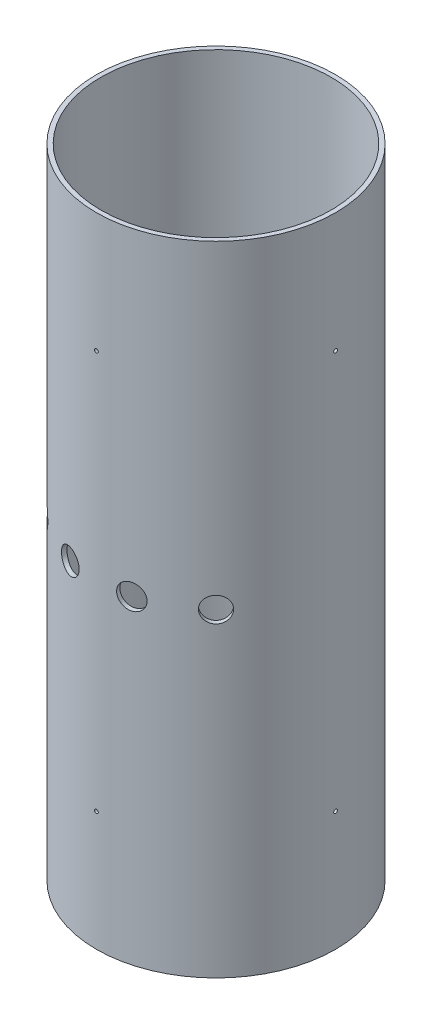
SolidWorks part; units mm, degrees
material "E-Glass Fiber"
ref_plane "Front Plane" through (0, 0, 0) normal (0, 0, 1) x (1, 0, 0)
ref_plane "Top Plane" through (0, 0, 0) normal (0, 1, 0) x (1, 0, 0)
ref_plane "Right Plane" through (0, 0, 0) normal (1, 0, 0) x (0, 0, -1)
sketch "Coupler Profile" plane through (0, 0, 0) normal (0, 1, 0) x (1, 0, 0)
  circle A0 centre (0, 0) radius 73.3425
  circle A1 centre (0, 0) radius 76.1746
  dimension "D1" = 146.685
  dimension "D2" = 152.3492
extrude "Coupler Body" add sketch "Coupler Profile" along normal blind 406.4
sketch "Sketch1" plane through (0, 0, 0) normal (0, 0, 1) x (1, 0, 0)
  line L0 (76.1746, 406.4) -> (-76.1746, 406.4) construction
  circle A0 centre (0, 76.2) radius 1.1906
  circle A1 centre (0, 330.2) radius 1.1906
  dimension "D3" = 2.3813
  dimension "D1" = 76.2
  dimension "D2" = 76.2
extrude "Cut-Extrude1" cut sketch "Sketch1" against normal through all both and the other way through all
pattern_circular "CirPattern1" count 4 over 360 about axis through (0, 0, 0) along (0, 1, 0) of "Cut-Extrude1"
sketch "Center Axis" plane through (0, 0, 0) normal (0, 0, 1) x (1, 0, 0)
  line L0 (0, 0) -> (0, 406.4) construction
  line L1 (73.3425, 406.4) -> (-73.3425, 406.4) construction
ref_plane "Offset Plane" through (0, 0, 0) normal (0.7071, 0, 0.7071) x (0, 1, 0)
sketch "Sketch3" plane through (0, 0, 0) normal (0.7071, 0, 0.7071) x (0, 1, 0)
  line L0 (0, 0) -> (406.4, 0) construction
  circle A0 centre (203.2, 0) radius 7.9375
  dimension "D1" = 15.875
extrude "Key Hole Cuts" cut sketch "Sketch3" along normal through all
pattern_circular "Key Hole Pattern" count 4 over 90 about axis through (0, 406.4, 0) along (0, 1, 0) of "Key Hole Cuts" reverse direction yes
sketch "Sketch4" plane through (0, 0, 0) normal (0, 0, 1) x (1, 0, 0)
  line L0 (-76.1746, 203.2) -> (76.1746, 203.2) construction
  line L1 (-76.1746, 329.0094) -> (-76.1746, 77.3906) construction
  line L2 (76.1746, 77.3906) -> (76.1746, 329.0094) construction
  circle A0 centre (0, 203.2) radius 3.175
  dimension "D1" = 6.35
extrude "Cut-Extrude2" cut sketch "Sketch4" against normal through all
ref_plane "Plane1" through (0, 330.1997, 0) normal (0, 1, 0) x (1, 0, 0)
sketch3d "3DSketch1"
  line L0 (-76.1746, 75.0094, 0) -> (0, 75.0094, 0) construction
  line L1 (0, 75.0094, 76.1746) -> (0, 75.0094, 0) construction
  spline S0 degree 3 poles (-76.1746, 75.0094, 0) (-76.1746, 75.0094, -0.0427) (-76.1745, 75.0132, -0.1253) (-76.1743, 75.0292, -0.2372) (-76.1738, 75.0564, -0.3498) (-76.1732, 75.0948, -0.4579) (-76.1726, 75.1441, -0.5614) (-76.1718, 75.2044, -0.6603) (-76.1709, 75.2758, -0.7547) (-76.1691, 75.4343, -0.9279) (-76.1662, 75.7306, -1.136) (-76.1648, 76.2008, -1.2181) (-76.1662, 76.6709, -1.1353) (-76.1694, 76.999, -0.9042) (-76.1718, 77.1995, -0.6651) (-76.1733, 77.3106, -0.4597) (-76.1743, 77.3758, -0.2422) (-76.1746, 77.3906, -0.0839) (-76.1746, 77.3906, 0) knots 0 0 0 0 0.032462 0.063988 0.094874 0.125434 0.155995 0.186881 0.218407 0.250871 0.375638 0.5004 0.625047 0.749699 0.813547 0.874851 0.936154 1 1 1 1 construction
  point P8 (0.1395, 77.3885, -0.0764)
  point P9 (1.6806, 75.0094, 0)
sketch "Sketch6" plane through (0, 330.1997, 0) normal (0, 1, 0) x (1, 0, 0)
  line L0 (0, 0) -> (-80.3653, 0)
  line L1 (0, 0) -> (0, -78.5899)
equation "\"Length\"=16"
equation "\"Outer Diameter\"= 5.998"
equation "\"Inner Diameter\"= 5.775"
equation "\"Wall Thickness\"= 0.111"
equation "\"D1@Coupler Profile\" = \"Inner Diameter\""
equation "\"D2@Coupler Profile\" = \"Outer Diameter\""
equation "\"D1@Coupler Body\" = \"Length\""
equation "\"Shear Pin Dia\"= 3 / 32"
equation "\"Shear Pin Offset\"= 3"
equation "\"D1@Sketch1\"=\"Shear Pin Offset\""
equation "\"D2@Sketch1\"=\"Shear Pin Offset\""
equation "\"D3@Sketch1\"=\"Shear Pin Dia\""
equation "\"Key Hole Dia\"= 0.625"
equation "\"D1@Sketch3\"=\"Key Hole Dia\""
